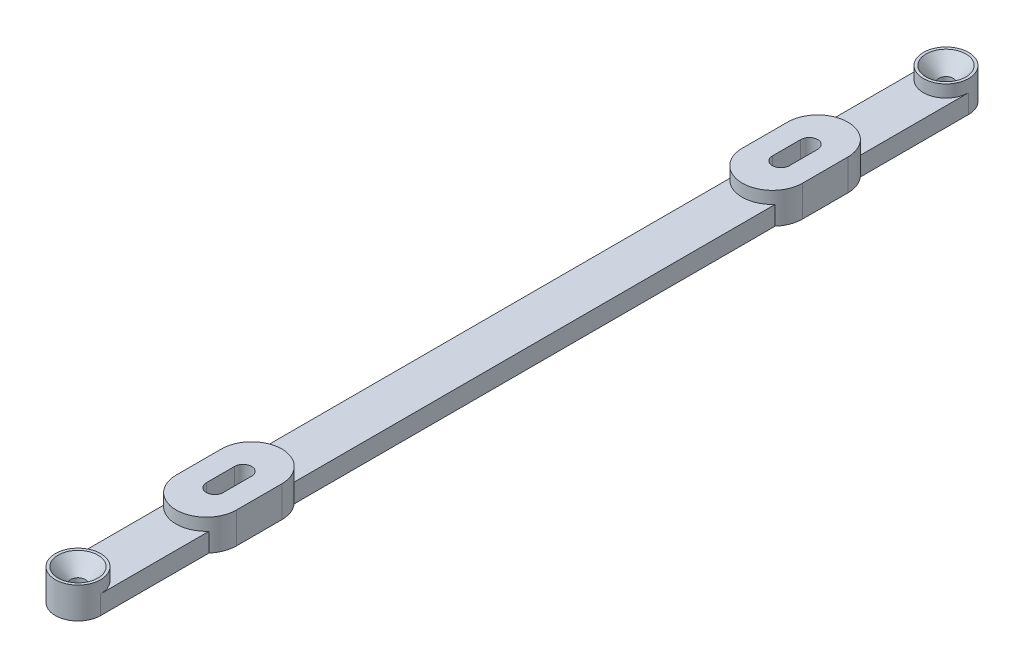
SolidWorks part; units mm, degrees
ref_plane "Front Plane" through (0, 0, 0) normal (0, 0, 1) x (1, 0, 0)
ref_plane "Top Plane" through (0, 0, 0) normal (0, 1, 0) x (1, 0, 0)
ref_plane "Right Plane" through (0, 0, 0) normal (1, 0, 0) x (0, 0, -1)
sketch "Arm Base Sketch" plane through (0, 0, 0) normal (0, 1, 0) x (1, 0, 0)
  line L0 (-6, 115) -> (6, 115)
  line L1 (6, 115) -> (6, 0)
  line L2 (6, 0) -> (-6, 0)
  line L3 (-6, 0) -> (-6, 115)
  point P2 (0, 0)
  dimension "D1" = 115
  dimension "D2" = 12
extrude "Arm Base Extrude" add sketch "Arm Base Sketch" along normal blind 5
sketch "Screw Bases Sketch" plane through (0, 0, 0) normal (0, -1, 0) x (1, 0, 0)
  line L0 (6, -115) -> (-6, -115) construction
  line L1 (0, -81) -> (0, -69) construction
  line L2 (-8, -81) -> (-8, -69)
  line L3 (8, -81) -> (8, -69)
  circle A0 centre (0, -115) radius 6
  arc A1 (-8, -81) -> (8, -81) centre (0, -81) ccw
  arc A2 (8, -69) -> (-8, -69) centre (0, -69) ccw
  point P8 (0, -75)
  dimension "D1" = 16
  dimension "D2" = 12
  dimension "D3" = 75
extrude "Screw Bases Extrude" add sketch "Screw Bases Sketch" against normal blind 8.25
hole_wizard "Power Supply Mounting Slot" positions "Power Supply Mounting Slot Position Sketch" profile "Power Supply Mounting Slot Profile Sketch" size "M4" standard "ANSI Metric" slot yes end condition through all
sketch "Power Supply Mounting Slot Position Sketch" plane through (0, 0, 0) normal (0, -1, 0) x (-1, 0, 0)
  line L0 (0, 81) -> (0, 69) construction
  line L1 (0, 81) -> (0, 69) construction
  point P0 (0, 75)
  point P13 (0, 0)
  point P14 (0, 0)
sketch "Power Supply Mounting Slot Profile Sketch" plane through (0, 0, -75) normal (1, 0, 0) x (0, 0, -1)
  line L0 (0, 0) -> (0, 8.25)
  line L1 (0, 8.25) -> (2.25, 8.25)
  line L3 (2.25, 8.25) -> (2.25, 3.1)
  line L4 (2.25, 3.1) -> (4.5, 3.1)
  line L5 (4.5, 3.1) -> (4.5, 0)
  line L7 (4.5, 0) -> (0, 0)
  line L11 (0, -6.35) -> (0, 107.95) construction
  dimension "Thru Hole Dia." = 4.5
  dimension "Thru Hole Depth" = 8.25
  dimension "C'Bore Dia." = 9
  dimension "C'Bore Depth" = 3.1
hole_wizard "No. 6 Mounting Screws" positions "No. 6 Mounting Screws Position Sketch" profile "No. 6 Mounting Screws Profile Sketch" countersink size "#6" standard "ANSI Inch" end condition through all
sketch "No. 6 Mounting Screws Position Sketch" plane through (0, 8.25, 0) normal (0, 1, 0) x (1, 0, 0)
  circle A0 centre (0, 115) radius 6 construction
  point P0 (0, 115)
sketch "No. 6 Mounting Screws Profile Sketch" plane through (0, 8.25, -115) normal (1, 0, 0) x (0, 0, 1)
  line L0 (0, 0) -> (0, 8.25)
  line L1 (0, 8.25) -> (1.8986, 8.25)
  line L2 (1.8986, 8.25) -> (1.8986, 3.8919)
  line L3 (1.8986, 3.8919) -> (5.2819, 0)
  line L5 (5.2819, 0) -> (0, 0)
  line L6 (-1.8987, 3.8919) -> (-5.2819, 0) construction
  line L11 (0, -6.35) -> (0, 107.95) construction
  dimension "Thru Hole Dia." = 3.7973
  dimension "Thru Hole Depth" = 8.25
  dimension "Near C'Sink Dia." = 10.5637
  dimension "Near C'Sink Angle" = 82
mirror "Mirror" about plane through (6, 5, 0) normal (0, 0, -1) of bodies 104
